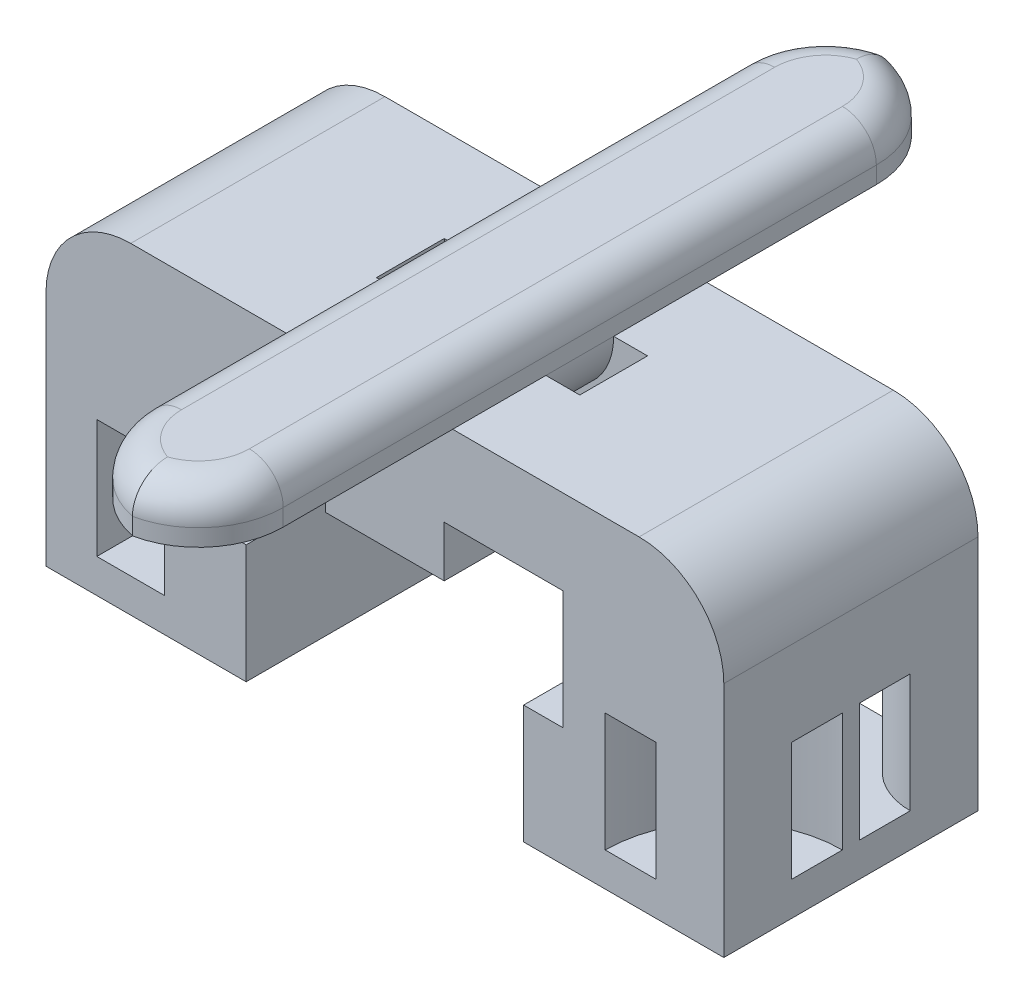
SolidWorks part; units mm, degrees
ref_plane "Plano frontal" through (0, 0, 0) normal (0, 0, 1) x (1, 0, 0)
ref_plane "Plano superior" through (0, 0, 0) normal (0, 1, 0) x (1, 0, 0)
ref_plane "Plano direito" through (0, 0, 0) normal (1, 0, 0) x (0, 0, -1)
sketch "Sketch1" plane through (0, 0, 0) normal (0, 0, 1) x (1, 0, 0)
  line L0 (-9.5, -5.0166) -> (2.3125, -5.0166)
  line L1 (2.3125, -5.0166) -> (2.3125, 1.9834)
  line L2 (2.3125, 1.9834) -> (0, 1.9834)
  line L3 (0, 1.9834) -> (0, 8.9834)
  line L4 (0, 8.9834) -> (7, 8.9834)
  line L5 (7, 8.9834) -> (7, 5.9834)
  line L6 (7, 5.9834) -> (14, 5.9834)
  line L7 (14, 5.9834) -> (14, 8.9834)
  line L8 (30.5, 4.176) -> (30.5, -5.0166)
  line L9 (30.5, 4.176) -> (30.5, 13.9834)
  line L10 (30.5, 13.9834) -> (-9.5, 13.9834)
  line L11 (-9.5, 13.9834) -> (-9.5, -5.0166)
  line L12 (30.5, -5.0166) -> (18.6875, -5.0166)
  line L13 (18.6875, -5.0166) -> (18.6875, 1.9834)
  line L14 (18.6875, 1.9834) -> (21, 1.9834)
  line L15 (21, 1.9834) -> (21, 8.9834)
  line L16 (21, 8.9834) -> (14, 8.9834)
  dimension "D1" = 7
  dimension "D2" = 3
  dimension "D3" = 7
  dimension "D4" = 7
  dimension "D5" = 7
  dimension "D6" = 5
  dimension "D7" = 40
extrude "Boss-Extrude3" add sketch "Sketch1" along normal blind 15
sketch "Sketch7" plane through (0, 13.9834, 0) normal (0, 1, 0) x (1, 0, 0)
  line L0 (-9.5, 0) -> (30.5, -15) construction
  line L1 (30.5, -15) -> (-9.5, -15) construction
  line L2 (6.5, 15) -> (14.5, 15)
  line L3 (6.5, 15) -> (6.5, -30)
  line L4 (6.5, -30) -> (14.5, -30)
  line L5 (14.5, 15) -> (14.5, -30)
  line L6 (6.5, 15) -> (14.5, -30) construction
  line L7 (6.5, -30) -> (14.5, 15) construction
  point P4 (10.5, -7.5)
  dimension "D1" = 15
  dimension "D2" = 8
extrude "Boss-Extrude5" add sketch "Sketch7" along normal blind 3
fillet "Fillet2" radius 5 4 edges at (14.5, 15.4834, -15) (6.5, 15.4834, -15) (6.5, 15.4834, 30) (14.5, 15.4834, 30)
fillet "Fillet3" radius 5 2 edges at (30.5, 13.9834, 7.5) (-9.5, 13.9834, 7.5)
fillet "Fillet4" radius 2 6 edges at (13.373, 16.9834, 28.1623) (7.627, 16.9834, 28.1623) (13.373, 16.9834, -13.1623) (7.627, 16.9834, -13.1623) (14.5, 16.9834, 7.5) (6.5, 16.9834, 7.5)
sketch "Sketch20" plane through (30.5, 0, 0) normal (1, 0, 0) x (0, 0, -1)
  line L0 (-15, -5.0166) -> (0, -5.0166) construction
  line L1 (-11, -3.0166) -> (-8, -3.0166)
  line L2 (-11, -3.0166) -> (-11, 3.9834)
  line L3 (-11, 3.9834) -> (-8, 3.9834)
  line L4 (-8, -3.0166) -> (-8, 3.9834)
  line L5 (-15, -5.0166) -> (-15, 8.9834) construction
  dimension "D1" = 2
  dimension "D2" = 4
  dimension "D3" = 7
  dimension "D4" = 3
revolve "Cut-Revolve10" cut sketch "Sketch20" angle 90 about axis through (30.5, 4.176, 15) along (0, 1, 0)
sketch "Sketch22" plane through (0, 13.9834, 0) normal (0, 1, 0) x (1, 0, 0)
  line L0 (10.5, 12.8284) -> (10.5, -27.8284) construction
  line L1 (4.5, -5.5) -> (6.5, -5.5)
  line L2 (4.5, -5.5) -> (4.5, -9.5)
  line L3 (4.5, -9.5) -> (6.5, -9.5)
  line L4 (6.5, -5.5) -> (6.5, -9.5)
  line L5 (6.5, 0) -> (6.5, -15) construction
  line L7 (6.5, 0) -> (-4.5, 0) construction
  dimension "D1" = 0
  dimension "D2" = 2
  dimension "D3" = 4
  dimension "D4" = 5.5
revolve "Cut-Revolve12" cut sketch "Sketch22" angle 180 about L0
sketch "Sketch23" plane through (0, 0, 0) normal (0, 0, -1) x (-1, 0, 0)
  line L0 (-18.6875, -5.0166) -> (-30.5, -5.0166) construction
  line L1 (-26.5, -3.0166) -> (-23.5, -3.0166)
  line L2 (-26.5, -3.0166) -> (-26.5, 3.9834)
  line L3 (-26.5, 3.9834) -> (-23.5, 3.9834)
  line L4 (-23.5, -3.0166) -> (-23.5, 3.9834)
  line L5 (-30.5, -5.0166) -> (-30.5, 8.9834) construction
  dimension "D1" = 2
  dimension "D2" = 4
  dimension "D3" = 7
  dimension "D4" = 3
revolve "Cut-Revolve13" cut sketch "Sketch23" angle 90 about axis through (30.5, 4.176, 0) along (0, 1, 0)
sketch "Sketch24" plane through (-9.5, 0, 0) normal (-1, 0, 0) x (0, 0, 1)
  line L0 (15, -5.0166) -> (0, -5.0166) construction
  line L1 (0, 8.9834) -> (0, -5.0166) construction
  text T0 "B" font "Comic Sans MS" height 12
  dimension "D1" = 1.5
  dimension "D2" = 2.75
extrude "Cut-Extrude7" cut sketch "Sketch24" against normal blind 1.5
sketch "Sketch25" plane through (0, 0, 0) normal (0, 0, -1) x (-1, 0, 0)
  line L0 (9.5, -5.0166) -> (-2.3125, -5.0166) construction
  line L1 (2.5, -3.0166) -> (6.5, -3.0166)
  line L2 (2.5, -3.0166) -> (2.5, 3.9834)
  line L3 (2.5, 3.9834) -> (6.5, 3.9834)
  line L4 (6.5, -3.0166) -> (6.5, 3.9834)
  line L6 (9.5, 8.9834) -> (9.5, -5.0166) construction
  dimension "D1" = 2
  dimension "D2" = 4
  dimension "D3" = 7
  dimension "D4" = 3
extrude "Cut-Extrude8" cut sketch "Sketch25" against normal up to next
